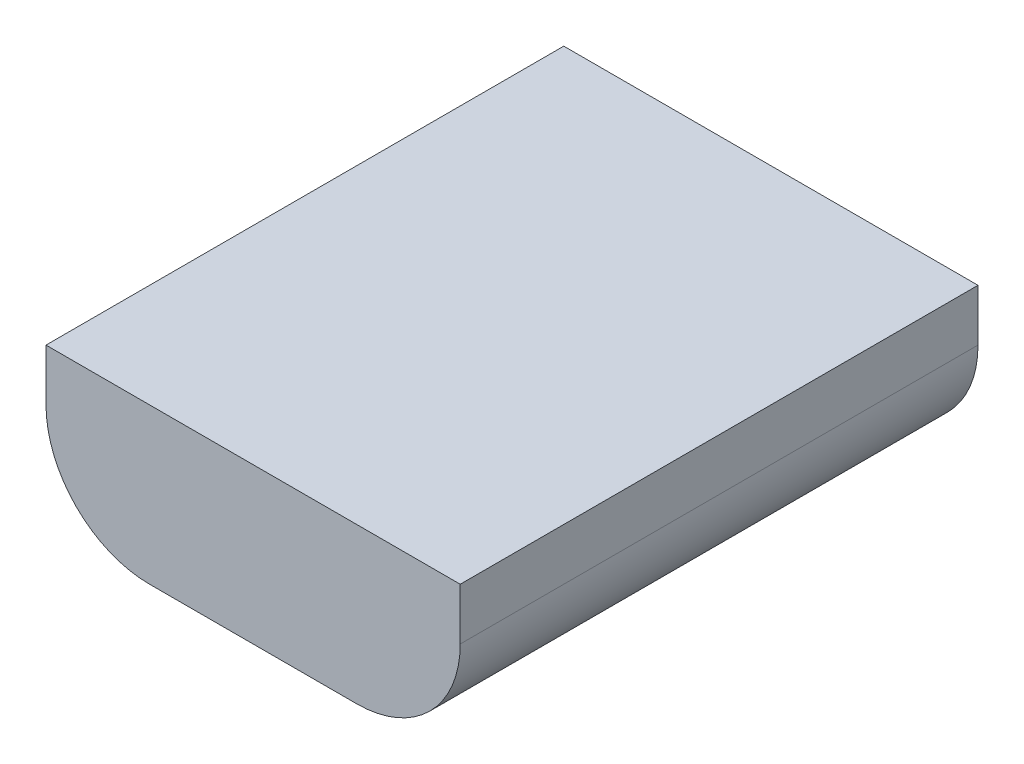
SolidWorks part; units mm, degrees
ref_plane "Front Plane" through (0, 0, 0) normal (0, 0, 1) x (1, 0, 0)
ref_plane "Top Plane" through (0, 0, 0) normal (0, 1, 0) x (1, 0, 0)
ref_plane "Right Plane" through (0, 0, 0) normal (1, 0, 0) x (0, 0, -1)
sketch "Sketch1" plane through (0, 0, 0) normal (0, 0, 1) x (1, 0, 0)
  line L0 (-20, 0) -> (20, 0)
  line L1 (40, 20) -> (40, 30)
  line L5 (0, -55) -> (0, 55) construction
  line L8 (-40, 20) -> (-40, 30)
  line L10 (-40, 30) -> (40, 30)
  arc A0 (20, 0) -> (40, 20) centre (20, 20) ccw
  arc A3 (-20, 0) -> (-40, 20) centre (-20, 20) cw
  point P0 (-20, 0)
  point P11 (0, 0)
  point P23 (0, 2)
  dimension "D1" = 20
  dimension "D2" = 10
  dimension "D3" = 40
extrude "Boss-Extrude1" add sketch "Sketch1" along normal blind 100
ref_plane "Plane1" through (0, 0, 100) normal (0, 0, 1) x (1, 0, 0)
ref_plane "Plane2" through (0, 0, -25) normal (0, 0, 1) x (1, 0, 0)
ref_plane "Plane3" through (0, 0, 0) normal (1, 0, 0) x (0, 0, -1)
